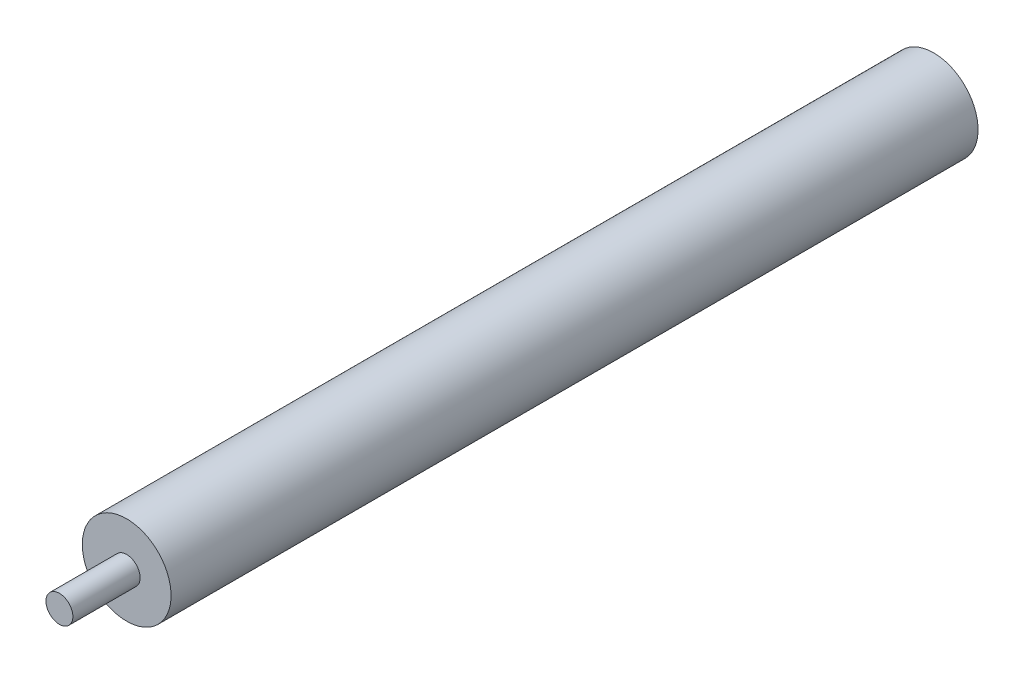
SolidWorks part; units mm, degrees
material "4032-T6"
ref_plane "Front Plane" through (0, 0, 0) normal (0, 0, 1) x (1, 0, 0)
ref_plane "Top Plane" through (0, 0, 0) normal (0, 1, 0) x (1, 0, 0)
ref_plane "Right Plane" through (0, 0, 0) normal (1, 0, 0) x (0, 0, -1)
sketch "Sketch1" plane through (0, 0, 0) normal (0, 0, 1) x (1, 0, 0)
  circle A0 centre (0, 0) radius 9.9
  dimension "D1" = 19.8
extrude "Boss-Extrude1" add sketch "Sketch1" along normal blind 180
sketch "Sketch2" plane through (0, 0, 180) normal (0, 0, 1) x (1, 0, 0)
  circle A0 centre (0, 0) radius 3
extrude "Boss-Extrude2" add sketch "Sketch2" along normal blind 15
